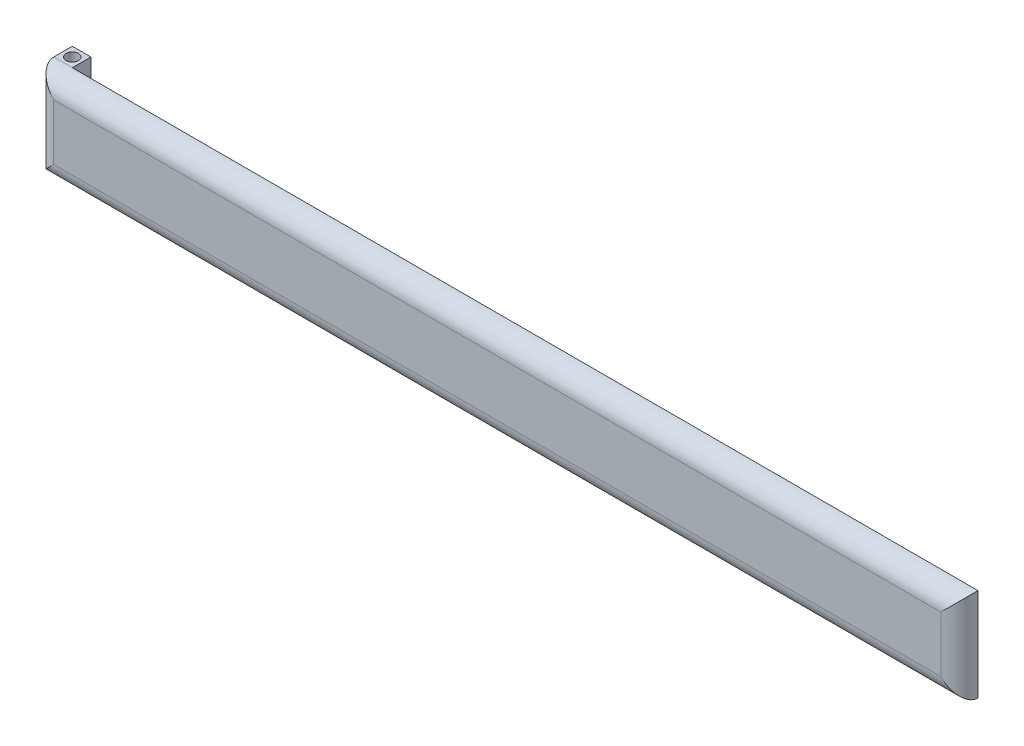
SolidWorks part; units mm, degrees
material "聚亚安酯(11671)"
ref_plane "前视基准面" through (0, 0, 0) normal (0, 0, 1) x (1, 0, 0)
ref_plane "上视基准面" through (0, 0, 0) normal (0, 1, 0) x (1, 0, 0)
ref_plane "右视基准面" through (0, 0, 0) normal (1, 0, 0) x (0, 0, -1)
sketch "草图1" plane through (0, 0, 0) normal (0, 0, 1) x (1, 0, 0)
  line L1 (-1.5, 7.5) -> (1.5, 7.5)
  line L2 (-1.5, 7.5) -> (-1.5, -7.5)
  line L3 (-1.5, -7.5) -> (1.5, -7.5)
  line L4 (1.5, 7.5) -> (1.5, -7.5)
  line L5 (-1.5, 7.5) -> (1.5, -7.5) construction
  line L6 (-1.5, -7.5) -> (1.5, 7.5) construction
  point P0 (0, 0)
  dimension "D1" = 3
  dimension "D2" = 15
extrude "凸台-拉伸1" add sketch "草图1" along normal blind 6
sketch "草图2" plane through (1.5, 0, 0) normal (1, 0, 0) x (0, 0, -1)
  line L0 (-6, 7.5) -> (0, 7.5) construction
  line L1 (-6, -7.5) -> (-3, -7.5)
  line L2 (-6, -7.5) -> (-6, 7.5)
  line L3 (-6, 7.5) -> (-3, 7.5)
  line L4 (-3, -7.5) -> (-3, 7.5)
  dimension "D1" = 3
extrude "凸台-拉伸2" add sketch "草图2" along normal blind 146
sketch "草图3" plane through (0, 7.5, 0) normal (0, 1, 0) x (1, 0, 0)
  circle A0 centre (0, -1.5) radius 1
  dimension "D2" = 2
extrude "切除-拉伸1" cut sketch "草图3" against normal blind 146
fillet "圆角1" radius 3 4 edges at (-1.5, 0, 6) (73, 7.5, 6) (147.5, 0, 6) (73, -7.5, 6)
